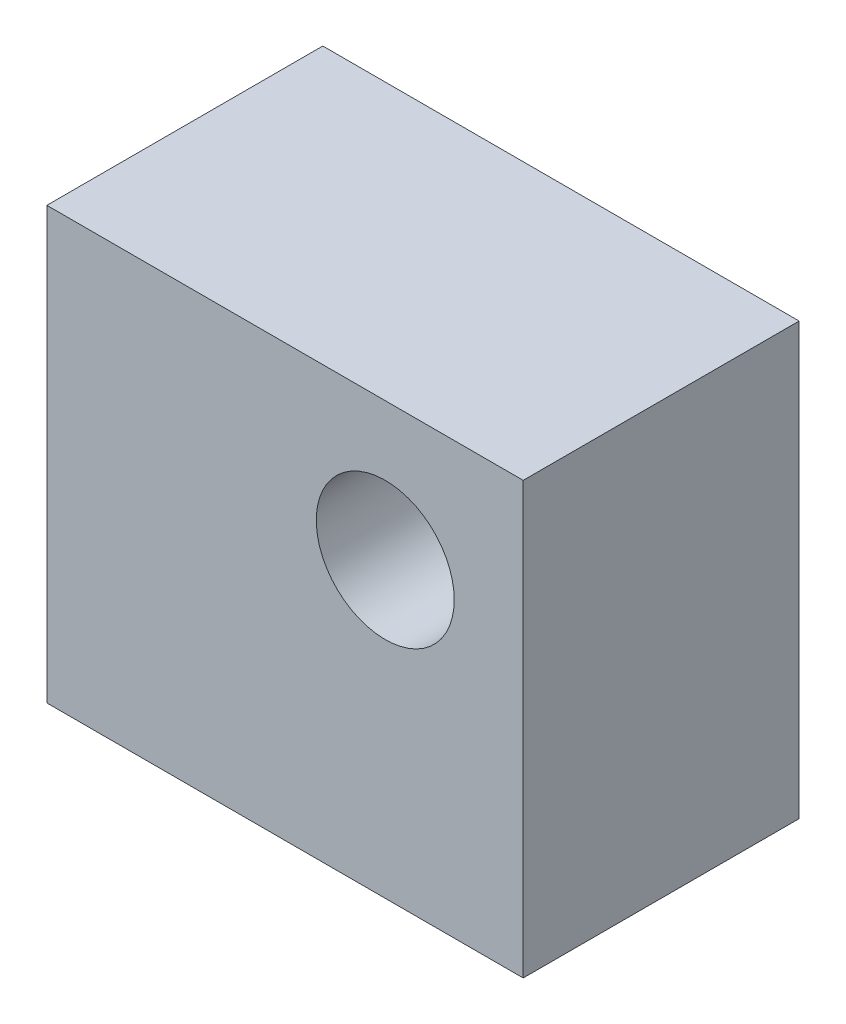
SolidWorks part; units mm, degrees
material "1060 Alloy"
ref_plane "Front" through (0, 0, 0) normal (0, 0, 1) x (1, 0, 0)
ref_plane "Top" through (0, 0, 0) normal (0, 1, 0) x (1, 0, 0)
ref_plane "Right" through (0, 0, 0) normal (1, 0, 0) x (0, 0, -1)
sketch "Sketch3" plane through (0, 0, 0) normal (0, 0, 1) x (1, 0, 0)
  line L0 (-0.127, -6.35) -> (30.1755, -6.35)
  line L1 (0, 0) -> (21.9242, 0)
  line L2 (0, 0) -> (0, -19.8376)
  line L3 (0, -19.8376) -> (21.9242, -19.8376)
  line L4 (21.9242, 0) -> (21.9242, -19.8376)
  line L5 (15.5742, -19.8376) -> (15.5742, 0) construction
  line L6 (15.5742, -6.35) -> (8.0621, -19.3614) construction
  line L15 (12.5496, -11.5887) -> (15.5742, -13.335) construction
  circle A0 centre (15.5742, -6.35) radius 6.0492 construction
  point P14 (0, -6.35)
  point P17 (9.525, -6.35)
  point P20 (7.7871, -19.8376)
  dimension "D2" = 6.35
  dimension "D6" = 3.4925
  dimension "D3" = 60
  dimension "D1" = 9.525
  dimension "D4" = 9.525
  dimension "D5" = 6.35
extrude "Boss-Extrude1" add sketch "Sketch3" along normal mid plane 12.7
sketch "Sketch4" plane through (0, 0, 0) normal (-1, 0, 0) x (0, 0, 1)
  circle A0 centre (0, -6.35) radius 3.175
  dimension "D1" = 6.35
extrude "Cut-Extrude1" cut sketch "Sketch4" against normal blind 9.525
ref_plane "Plane1" through (7.7871, -19.8376, 0) normal (-0.5, -0.866, 0) x (-0.866, 0.5, 0)
ref_plane "Mirror Plane" through (15.5742, 0, 0) normal (-1, 0, 0) x (0, 0, 1)
sketch "Sketch5" plane through (7.7871, -19.8376, 0) normal (-0.5, -0.866, 0) x (-0.866, 0.5, 0)
  circle A0 centre (0, 0) radius 3.175
  dimension "D1" = 6.35
extrude "Cut-Extrude5" cut sketch "Sketch5" against normal blind 9.525 and the other way up to next
sketch "Sketch6" plane through (0, 0, 6.35) normal (0, 0, -1) x (-1, 0, 0)
  circle A0 centre (-15.5742, -6.35) radius 3.175
  dimension "D1" = 6.35
extrude "Cut-Extrude6" cut sketch "Sketch6" along normal blind 9.525
equation "\"truss_member_od\" = .25in"
equation "\"truss_member_id\" = 0in"
equation "\"truss_member_L1\" = 2.75in"
equation "\"connector_hole_depth\" = .375in"
equation "\"D1@Boss-Extrude1\"=\"truss_member_od\"*2"
equation "\"D6@Sketch3\"=\"truss_member_od\"/2*1.1"
equation "\"D1@Sketch4\"=\"truss_member_od\""
equation "\"D1@Cut-Extrude1\"=\"connector_hole_depth\""
equation "\"D1@Sketch3\"=\"connector_hole_depth\""
equation "\"D4@Sketch3\"=\"connector_hole_depth\""
equation "\"D1@Sketch5\"=\"truss_member_od\""
equation "\"D1@Cut-Extrude5\"=\"connector_hole_depth\""
equation "\"D1@Cut-Extrude6\"=\"connector_hole_depth\""
equation "\"D1@Sketch6\"=\"truss_member_od\""
equation "\"D5@Sketch3\"=\"truss_member_od\""
